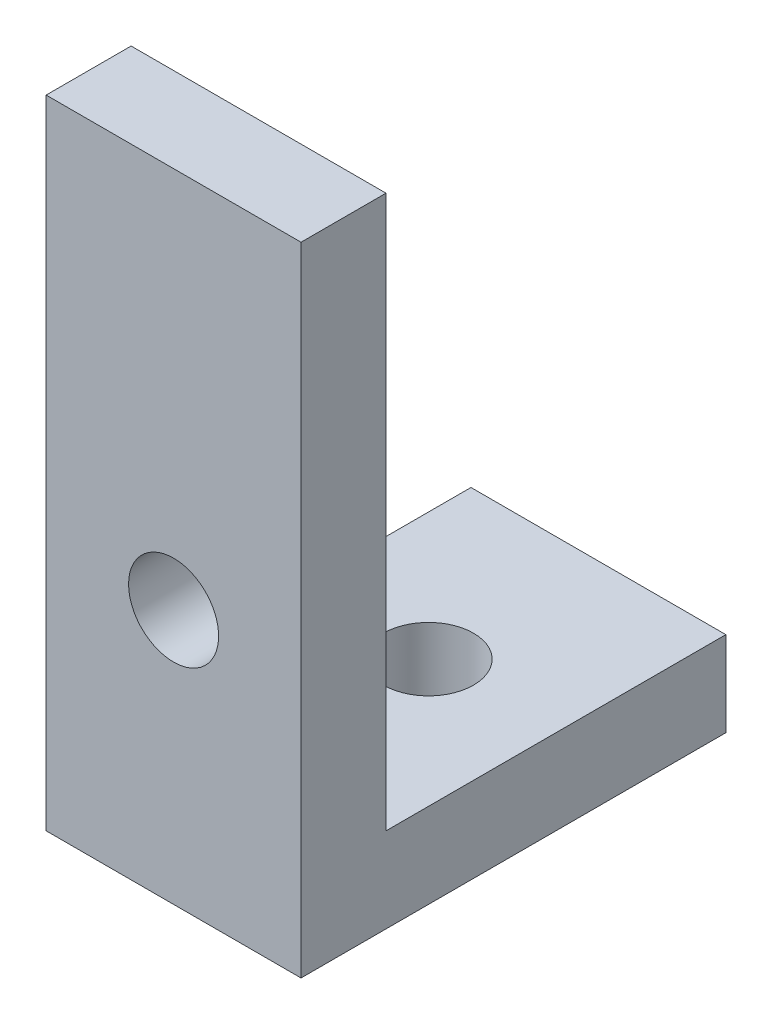
SolidWorks part; units mm, degrees
ref_plane "Front Plane" through (0, 0, 0) normal (0, 0, 1) x (1, 0, 0)
ref_plane "Top Plane" through (0, 0, 0) normal (0, 1, 0) x (1, 0, 0)
ref_plane "Right Plane" through (0, 0, 0) normal (1, 0, 0) x (0, 0, -1)
sketch "Sketch2" plane through (0, 0, 0) normal (0, 0, 1) x (1, 0, 0)
  line L1 (0, 0) -> (15, 0)
  line L2 (0, 0) -> (0, 37.5)
  line L3 (0, 37.5) -> (15, 37.5)
  line L4 (15, 0) -> (15, 37.5)
  dimension "D1" = 37.5
  dimension "D2" = 15
extrude "Boss-Extrude1" add sketch "Sketch2" along normal blind 5
sketch "Sketch3" plane through (0, 0, 0) normal (0, 0, 1) x (1, 0, 0)
  line L0 (15, 0) -> (15, 37.5) construction
  line L1 (0, 0) -> (15, 0)
  line L2 (0, 0) -> (0, 5)
  line L3 (0, 5) -> (15, 5)
  line L4 (15, 0) -> (15, 5)
  dimension "D1" = 5
extrude "Boss-Extrude2" add sketch "Sketch3" against normal blind 20
sketch "Sketch6" plane through (0, 0, 0) normal (0, -1, 0) x (1, 0, 0)
  line L0 (0, -20) -> (15, -20) construction
  line L1 (0, -20) -> (0, 5) construction
  circle A0 centre (7.5, -10) radius 2.65
  dimension "D1" = 5.3
  dimension "D2" = 10
  dimension "D3" = 7.5
extrude "Cut-Extrude2" cut sketch "Sketch6" against normal blind 10
sketch "Sketch7" plane through (0, 0, 0) normal (0, 0, -1) x (-1, 0, 0)
  line L0 (0, 0) -> (-15, 0) construction
  line L1 (0, 37.5) -> (0, 5) construction
  circle A0 centre (-7.5, 15) radius 2.65
  dimension "D1" = 5.3
  dimension "D2" = 15
  dimension "D3" = 7.5
extrude "Cut-Extrude3" cut sketch "Sketch7" against normal blind 10
